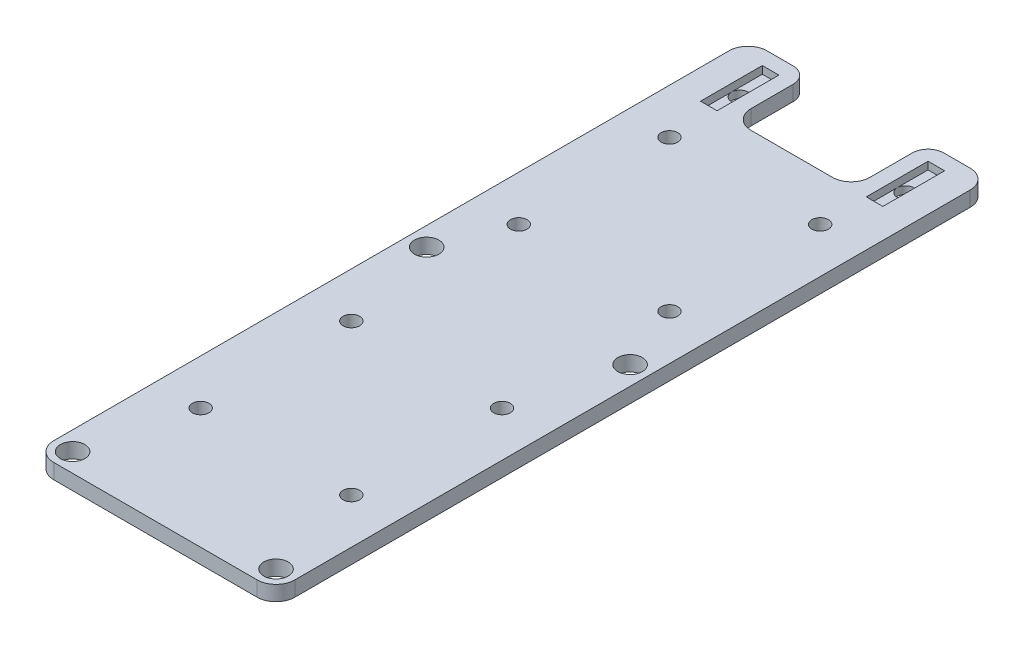
SolidWorks part; units mm, degrees
ref_plane "Front Plane" through (0, 0, 0) normal (0, 0, 1) x (1, 0, 0)
ref_plane "Top Plane" through (0, 0, 0) normal (0, 1, 0) x (1, 0, 0)
ref_plane "Right Plane" through (0, 0, 0) normal (1, 0, 0) x (0, 0, -1)
sketch "Sketch1" plane through (0, 0, 0) normal (0, 1, 0) x (1, 0, 0)
  line L0 (0, 42.225) -> (0, -42.225) construction
  line L1 (16, 42.225) -> (-16, 42.225)
  line L2 (16, 42.225) -> (16, -42.225)
  line L3 (16, -42.225) -> (-16, -42.225)
  line L4 (-16, 42.225) -> (-16, -42.225)
  line L5 (16, 42.225) -> (-16, -42.225) construction
  line L6 (16, -42.225) -> (-16, 42.225) construction
  line L12 (-12.1, 50.425) -> (-12.1, 52.425) construction
  line L17 (-11, 52.425) -> (-11, 42.225) construction
  line L18 (-7.9, 42.225) -> (-14.1, 42.225)
  line L20 (-10, 36) -> (10, 36)
  line L21 (-10, 36) -> (-10, 16)
  line L22 (-10, 16) -> (10, 16)
  line L23 (10, 36) -> (10, 16)
  line L24 (-10, 36) -> (10, 16) construction
  line L25 (-10, 16) -> (10, 36) construction
  line L26 (-14.5, 10.775) -> (14.5, 10.775)
  line L27 (-14.5, 10.775) -> (-14.5, 41.225)
  line L28 (-14.5, 41.225) -> (14.5, 41.225)
  line L29 (14.5, 10.775) -> (14.5, 41.225)
  line L30 (-14.5, 10.775) -> (14.5, 41.225) construction
  line L31 (-14.5, 41.225) -> (14.5, 10.775) construction
  line L32 (-10, -6.225) -> (10, -6.225)
  line L33 (-10, -6.225) -> (-10, -26.225)
  line L34 (-10, -26.225) -> (10, -26.225)
  line L35 (10, -6.225) -> (10, -26.225)
  line L36 (-10, -6.225) -> (10, -26.225) construction
  line L37 (-10, -26.225) -> (10, -6.225) construction
  line L38 (-15.75, -36.225) -> (15.75, -36.225)
  line L39 (-15.75, -36.225) -> (-15.75, 3.775)
  line L40 (-15.75, 3.775) -> (15.75, 3.775)
  line L41 (15.75, -36.225) -> (15.75, 3.775)
  line L42 (-15.75, -36.225) -> (15.75, 3.775) construction
  line L43 (-15.75, 3.775) -> (15.75, -36.225) construction
  line L48 (-7.9, 42.225) -> (-7.9, 52.425)
  line L49 (-7.9, 52.425) -> (-14.1, 52.425)
  line L59 (-14.1, 42.225) -> (-14.1, 52.425)
  line L63 (-12.1, 50.425) -> (-9.9, 50.425)
  line L64 (-12.1, 50.425) -> (-12.1, 42.225)
  line L65 (-12.1, 42.225) -> (-9.9, 42.225)
  line L66 (-9.9, 50.425) -> (-9.9, 42.225)
  line L67 (-12.1, 50.425) -> (-9.9, 42.225) construction
  line L68 (-12.1, 42.225) -> (-9.9, 50.425) construction
  line L69 (-12.1, 50.425) -> (-14.1, 50.425) construction
  line L74 (7.9, 42.225) -> (14.1, 42.225)
  line L75 (14.1, 42.225) -> (14.1, 52.425)
  line L76 (7.9, 52.425) -> (14.1, 52.425)
  line L77 (7.9, 42.225) -> (7.9, 52.425)
  line L78 (12.1, 50.425) -> (9.9, 50.425)
  line L79 (12.1, 50.425) -> (12.1, 42.225)
  line L80 (12.1, 42.225) -> (9.9, 42.225)
  line L81 (9.9, 50.425) -> (9.9, 42.225)
  line L82 (-14.5, 10.775) -> (-14.5, 3.775) construction
  line L83 (-14.5, 7.275) -> (16, 7.275) construction
  line L89 (-13.5, -37.225) -> (-16, -37.225) construction
  line L94 (-14.1, 52.425) -> (-16, 52.425)
  line L95 (-14.1, 52.425) -> (-14.1, 42.225)
  line L96 (-14.1, 42.225) -> (-16, 42.225)
  line L97 (-16, 52.425) -> (-16, 42.225)
  line L98 (14.1, 52.425) -> (16, 52.425)
  line L99 (14.1, 52.425) -> (14.1, 42.225)
  line L100 (14.1, 42.225) -> (16, 42.225)
  line L101 (16, 52.425) -> (16, 42.225)
  circle A3 centre (-10, 36) radius 1.1
  circle A4 centre (10, 36) radius 1.1
  circle A5 centre (10, 16) radius 1.1
  circle A6 centre (-10, 16) radius 1.1
  circle A7 centre (-10, -6.225) radius 1.1
  circle A8 centre (10, -6.225) radius 1.1
  circle A9 centre (10, -26.225) radius 1.1
  circle A10 centre (-10, -26.225) radius 1.1
  circle A37 centre (-13.5, 7.275) radius 2.5
  circle A38 centre (-13.5, 7.275) radius 1.625
  circle A39 centre (13.5, 7.275) radius 1.625
  circle A40 centre (-13.5, -39.725) radius 2.5
  circle A41 centre (-13.5, -39.725) radius 1.625
  circle A42 centre (13.5, -39.725) radius 1.625
  point P0 (0, 0)
  point P8 (0, 0)
  point P16 (0, 26)
  point P26 (0, 26)
  point P31 (0, -16.225)
  point P36 (0, -16.225)
  point P61 (-11, 46.325)
  dimension "D3" = 2
  dimension "D17" = 2.2
  dimension "D22" = 5
  dimension "D23" = 3.25
  dimension "D8" = 32
  dimension "D9" = 22
  dimension "D10" = 20
  dimension "D11" = 29
  dimension "D12" = 30.45
  dimension "D13" = 40
  dimension "D14" = 31.5
  dimension "D15" = 1
  dimension "D16" = 7
  dimension "D18" = 2.2
  dimension "D20" = 8.2
  dimension "D24" = 1
extrude "Boss-Extrude1" add sketch "Sketch1" along normal blind 2 contours L63 L66 L1 L48 L49 L59 L18 L64 | L81 L78 L79 L1 L75 L76 L77 | L94 L97 L1 L59 | L101 L98 L75 L1 | L1 L4 L3 L2 | A4 | A3 | A7 | A8 | A9 | A10 | A5 | A6 | A39 | A38 | A41 | A42 region at (15.05, 0, -47.325) region at (13.1, 0, -42.3444) region at (-8.9, 0, -42.3444) region at (-15.05, 0, -47.325)
sketch "Sketch2" plane through (0, 0, 0) normal (0, -1, 0) x (1, 0, 0)
  line L0 (-12.1, -42.225) -> (-9.9, -50.425) construction
  line L1 (12.1, -42.225) -> (9.9, -50.425) construction
  line L4 (12.1, -42.225) -> (9.9, -42.225)
  line L5 (12.1, -50.425) -> (12.1, -42.225)
  line L6 (9.9, -50.425) -> (12.1, -50.425)
  line L7 (9.9, -42.225) -> (9.9, -50.425)
  line L8 (12.1, -42.225) -> (9.9, -42.225)
  line L9 (12.1, -50.425) -> (12.1, -42.225)
  line L10 (9.9, -50.425) -> (12.1, -50.425)
  line L11 (9.9, -42.225) -> (9.9, -50.425)
  line L12 (-9.9, -42.225) -> (-12.1, -42.225)
  line L13 (-9.9, -50.425) -> (-9.9, -42.225)
  line L14 (-12.1, -50.425) -> (-9.9, -50.425)
  line L15 (-12.1, -42.225) -> (-12.1, -50.425)
  line L16 (-9.9, -42.225) -> (-12.1, -42.225)
  line L17 (-9.9, -50.425) -> (-9.9, -42.225)
  line L18 (-12.1, -50.425) -> (-9.9, -50.425)
  line L19 (-12.1, -42.225) -> (-12.1, -50.425)
  circle A0 centre (-11, -46.325) radius 1.1
  circle A1 centre (11, -46.325) radius 1.1
  line M9 (9.9, -42.225) -> (12.1, -42.225)
  line M10 (12.1, -42.225) -> (12.1, -50.425)
  line M11 (12.1, -50.425) -> (9.9, -50.425)
  line M12 (9.9, -50.425) -> (9.9, -42.225)
  line M13 (-12.1, -42.225) -> (-9.9, -42.225)
  line M14 (-9.9, -42.225) -> (-9.9, -50.425)
  line M15 (-9.9, -50.425) -> (-12.1, -50.425)
  line M16 (-12.1, -50.425) -> (-12.1, -42.225)
  dimension "D1" = 0
  dimension "D2" = 0
extrude "Boss-Extrude2" add sketch "Sketch2" against normal offset from surface (1 mm away) 1 contours A0 L19 M14 M13 | A0 L17 M16 M15 | A1 L9 M12 M11 | A1 L11 M10 M9 region at (11, 0, -43.8523) region at (11, 0, -48.7977) region at (-11, 0, -43.8523) region at (-11, 0, -48.7977) up to face at (11, 2, -46.325)
fillet "Fillet1" radius 2.5 6 edges at (7.9, 1, -42.225) (-7.9, 1, -42.225) (-16, 1, -52.425) (16, 1, -52.425) (-16, 1, 42.225) (16, 1, 42.225)
fillet "Fillet2" radius 2.1 2 edges at (-7.9, 1, -52.425) (7.9, 1, -52.425)
sketch "Sketch3" [suppressed] plane through (0, 2, 0) normal (0, 1, 0) x (1, 0, 0)
  line L6 (12.1, 42.225) -> (12.1, 50.425)
  line L7 (9.9, 42.225) -> (12.1, 42.225)
  line L8 (-10.4, 52.425) -> (-13.5, 52.425)
  line L9 (-16, 49.925) -> (-16, -39.725)
  line L10 (-13.5, -42.225) -> (13.5, -42.225)
  line L11 (16, -39.725) -> (16, 49.925)
  line L12 (13.5, 52.425) -> (10.4, 52.425)
  line L13 (7.9, 49.925) -> (7.9, 44.725)
  line L14 (5.4, 42.225) -> (-5.4, 42.225)
  line L15 (-7.9, 44.725) -> (-7.9, 49.925)
  line L16 (-10.4, 52.425) -> (-13.5, 52.425)
  line L17 (-16, 49.925) -> (-16, -39.725)
  line L18 (-13.5, -42.225) -> (13.5, -42.225)
  line L19 (16, -39.725) -> (16, 49.925)
  line L20 (13.5, 52.425) -> (10.4, 52.425)
  line L21 (7.9, 49.925) -> (7.9, 44.725)
  line L22 (5.4, 42.225) -> (-5.4, 42.225)
  line L23 (-7.9, 44.725) -> (-7.9, 49.925)
  line L24 (9.9, 50.425) -> (9.9, 42.225)
  line L25 (12.1, 50.425) -> (9.9, 50.425)
  line L26 (12.1, 42.225) -> (12.1, 50.425)
  line L27 (9.9, 42.225) -> (12.1, 42.225)
  line L28 (9.9, 50.425) -> (9.9, 42.225)
  line L29 (12.1, 50.425) -> (9.9, 50.425)
  line L30 (-9.9, 42.225) -> (-9.9, 50.425)
  line L31 (-12.1, 42.225) -> (-9.9, 42.225)
  line L32 (-12.1, 50.425) -> (-12.1, 42.225)
  line L33 (-9.9, 50.425) -> (-12.1, 50.425)
  line L34 (-9.9, 42.225) -> (-9.9, 50.425)
  line L35 (-12.1, 42.225) -> (-9.9, 42.225)
  line L36 (-12.1, 50.425) -> (-12.1, 42.225)
  line L37 (-9.9, 50.425) -> (-12.1, 50.425)
  circle A0 centre (13.5, -39.725) radius 1.625 construction
  circle A1 centre (-13.5, -39.725) radius 1.625 construction
  circle A2 centre (-13.5, 7.275) radius 1.625 construction
  circle A3 centre (-10, -6.225) radius 1.1 construction
  circle A4 centre (-10, -26.225) radius 1.1 construction
  circle A5 centre (10, -26.225) radius 1.1 construction
  circle A6 centre (10, -6.225) radius 1.1 construction
  circle A7 centre (13.5, 7.275) radius 1.625 construction
  arc A8 (-13.5, 52.425) -> (-16, 49.925) centre (-13.5, 49.925) ccw
  arc A9 (-16, -39.725) -> (-13.5, -42.225) centre (-13.5, -39.725) ccw
  arc A10 (13.5, -42.225) -> (16, -39.725) centre (13.5, -39.725) ccw
  arc A11 (16, 49.925) -> (13.5, 52.425) centre (13.5, 49.925) ccw
  arc A12 (10.4, 52.425) -> (7.9, 49.925) centre (10.4, 49.925) ccw
  arc A13 (5.4, 42.225) -> (7.9, 44.725) centre (5.4, 44.725) ccw
  arc A14 (-7.9, 44.725) -> (-5.4, 42.225) centre (-5.4, 44.725) ccw
  arc A15 (-7.9, 49.925) -> (-10.4, 52.425) centre (-10.4, 49.925) ccw
  arc A16 (-13.5, 52.425) -> (-16, 49.925) centre (-13.5, 49.925) ccw
  arc A17 (-16, -39.725) -> (-13.5, -42.225) centre (-13.5, -39.725) ccw
  arc A18 (13.5, -42.225) -> (16, -39.725) centre (13.5, -39.725) ccw
  arc A19 (16, 49.925) -> (13.5, 52.425) centre (13.5, 49.925) ccw
  arc A20 (10.4, 52.425) -> (7.9, 49.925) centre (10.4, 49.925) ccw
  arc A21 (5.4, 42.225) -> (7.9, 44.725) centre (5.4, 44.725) ccw
  arc A22 (-7.9, 44.725) -> (-5.4, 42.225) centre (-5.4, 44.725) ccw
  arc A23 (-7.9, 49.925) -> (-10.4, 52.425) centre (-10.4, 49.925) ccw
  circle A24 centre (-10, 16) radius 1.1 construction
  circle A25 centre (-10, 36) radius 1.1 construction
  circle A26 centre (10, 36) radius 1.1 construction
  circle A27 centre (10, 16) radius 1.1 construction
  circle A28 centre (10, 16) radius 1.1
  circle A29 centre (10, 36) radius 1.1
  circle A30 centre (-10, 36) radius 1.1
  circle A31 centre (-10, 16) radius 1.1
  circle A32 centre (13.5, 7.275) radius 1.625
  circle A33 centre (10, -6.225) radius 1.1
  circle A34 centre (10, -26.225) radius 1.1
  circle A35 centre (-10, -26.225) radius 1.1
  circle A36 centre (-10, -6.225) radius 1.1
  circle A37 centre (13.5, -39.725) radius 1.625
  circle A38 centre (-13.5, -39.725) radius 1.625
  circle A39 centre (-13.5, 7.275) radius 1.625
  dimension "D1" = 0
  dimension "D2" = 0
  dimension "D3" = 0
extrude "Boss-Extrude3" [suppressed] add sketch "Sketch3" along normal blind 1
